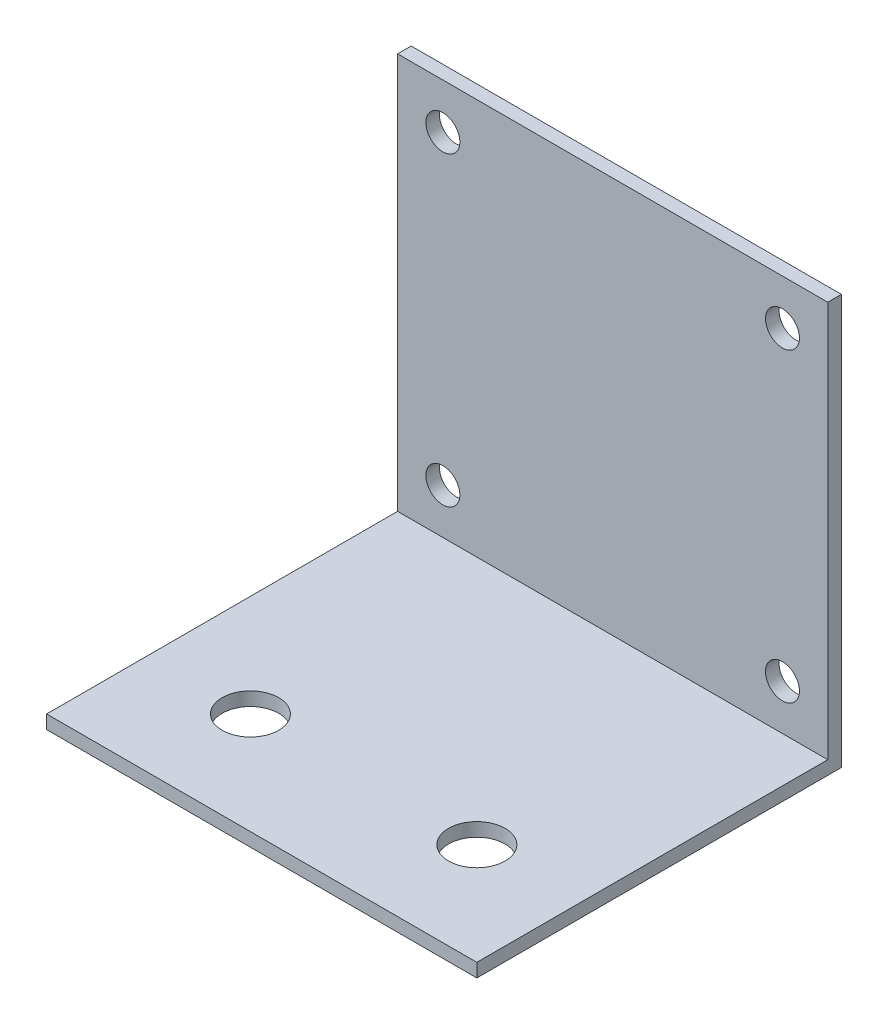
SolidWorks part; units mm, degrees
ref_plane "Front Plane" through (0, 0, 0) normal (0, 0, 1) x (1, 0, 0)
ref_plane "Top Plane" through (0, 0, 0) normal (0, 1, 0) x (1, 0, 0)
ref_plane "Right Plane" through (0, 0, 0) normal (1, 0, 0) x (0, 0, -1)
sketch "Sketch1" plane through (0, 0, 0) normal (0, 1, 0) x (1, 0, 0)
  line L0 (-19, 0) -> (-19, -32.2) construction
  line L1 (0, 0) -> (-38, 0)
  line L2 (0, 0) -> (0, -32.2)
  line L3 (0, -32.2) -> (-38, -32.2)
  line L4 (-38, 0) -> (-38, -32.2)
  circle A0 centre (-29, -23.2) radius 2.5
  circle A2 centre (-9, -23.2) radius 2.5
  dimension "D3" = 5
  dimension "D4" = 9
  dimension "D5" = 10
  dimension "D1" = 32.2
  dimension "D2" = 38
extrude "Boss-Extrude1" add sketch "Sketch1" along normal blind 1.2
sketch "Sketch2" plane through (0, 1.2, 0) normal (0, 1, 0) x (1, 0, 0)
  line L0 (0, -32.2) -> (0, 0) construction
  line L1 (-38, 0) -> (0, 0)
  line L2 (-38, 0) -> (-38, -1.2)
  line L3 (-38, -1.2) -> (0, -1.2)
  line L4 (0, 0) -> (0, -1.2)
  dimension "D1" = 1.2
extrude "Boss-Extrude2" add sketch "Sketch2" along normal blind 35
sketch "Sketch3" plane through (0, 0, 1.2) normal (0, 0, 1) x (1, 0, 0)
  line L0 (-19, 36.2) -> (-19, 1.2) construction
  line L1 (-38, 36.2) -> (0, 36.2) construction
  line L2 (-38, 1.2) -> (0, 1.2) construction
  line L3 (-38, 1.2) -> (0, 1.2) construction
  line L4 (-38, 36.2) -> (-38, 1.2) construction
  circle A0 centre (-34, 5.2) radius 1.5
  circle A1 centre (-34, 32.2) radius 1.5
  circle A2 centre (-4, 5.2) radius 1.5
  circle A3 centre (-4, 32.2) radius 1.5
  dimension "D1" = 4
  dimension "D2" = 4
  dimension "D3" = 4
  dimension "D4" = 3
  dimension "D5" = 4
  dimension "D6" = 3
extrude "Cut-Extrude1" cut sketch "Sketch3" against normal through all
